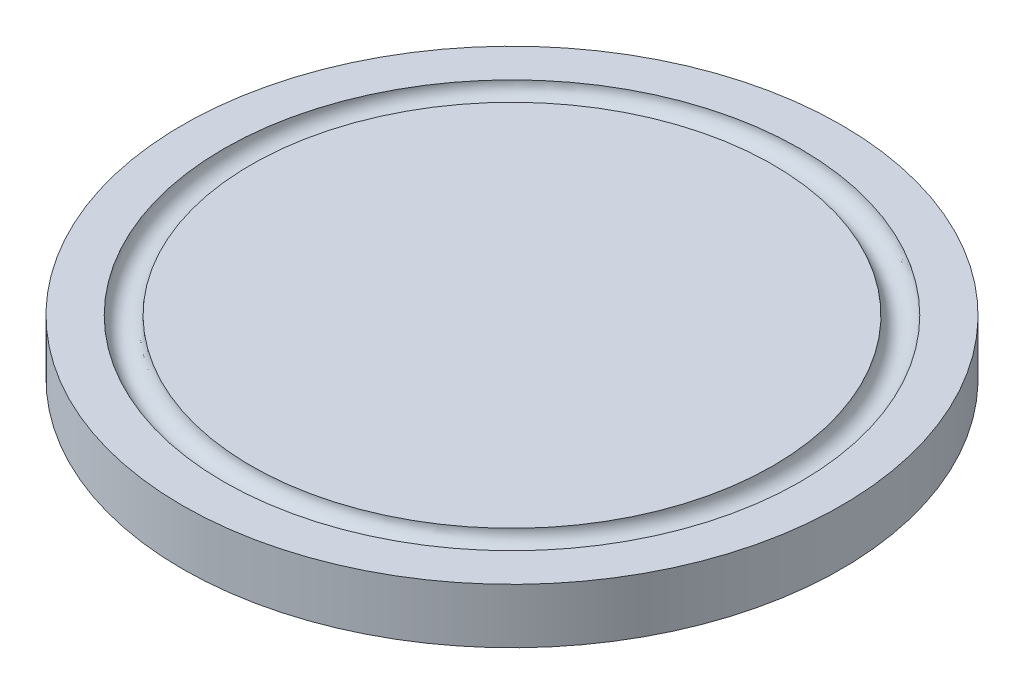
SolidWorks part; units mm, degrees
ref_plane "Front Plane" through (0, 0, 0) normal (0, 0, 1) x (1, 0, 0)
ref_plane "Top Plane" through (0, 0, 0) normal (0, 1, 0) x (1, 0, 0)
ref_plane "Right Plane" through (0, 0, 0) normal (1, 0, 0) x (0, 0, -1)
sketch "Sketch1" plane through (0, 0, 0) normal (0, 1, 0) x (1, 0, 0)
  circle A0 centre (0, 0) radius 60
  dimension "D1" = 120
extrude "Boss-Extrude1" add sketch "Sketch1" along normal blind 10
sketch "Sketch2" plane through (0, 10, 0) normal (0, 1, 0) x (1, 0, 0)
  circle A0 centre (0, 0) radius 50
  dimension "Bearing Ball Track Diameter" = 100
sketch "Sketch3" plane through (0, 0, 0) normal (0, 0, 1) x (1, 0, 0)
  line L0 (50, 10) -> (-50, 10) construction
  line L1 (0, 0) -> (0, 10) construction
  line L2 (0, 10) -> (50, 10) construction
  circle A0 centre (50, 10) radius 2.5
  dimension "Bearing Ball OD" = 5
  dimension "Bearing Ball Track Radius" = 50
sweep "Cut-Sweep1" cut profiles "Sketch3" path "Sketch2"
